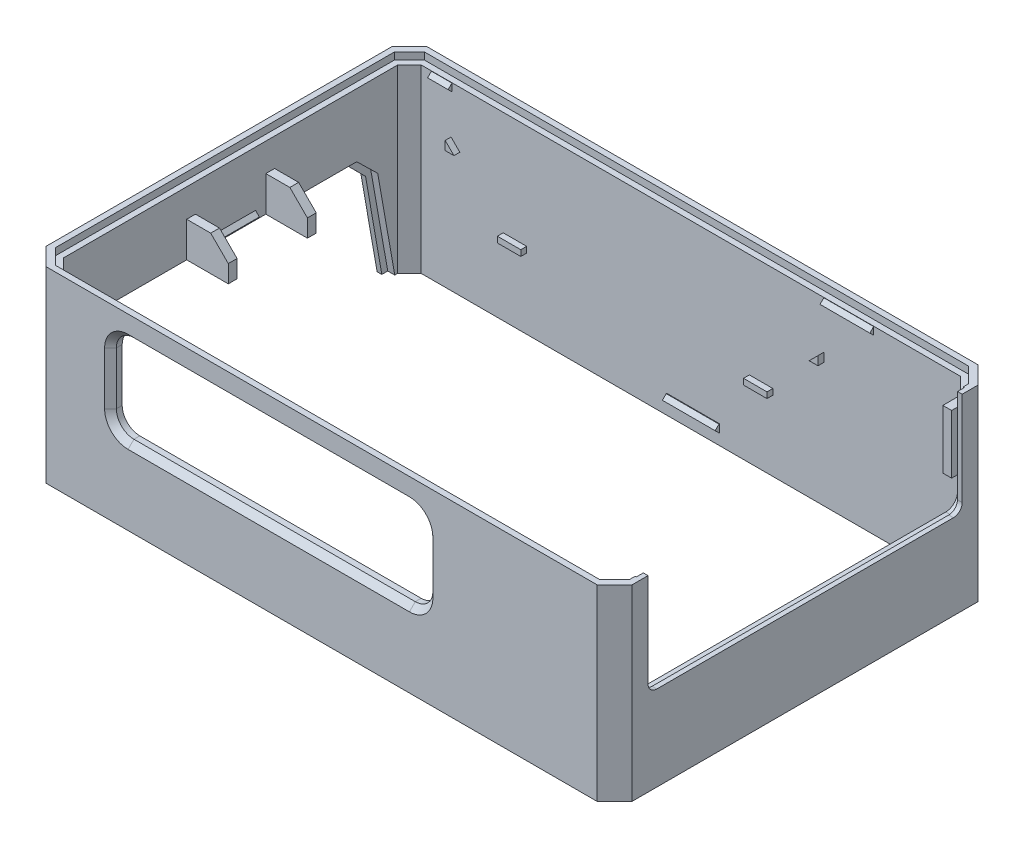
SolidWorks part; units mm, degrees
ref_plane "前视基准面" through (0, 0, 0) normal (0, 0, 1) x (1, 0, 0)
ref_plane "上视基准面" through (0, 0, 0) normal (0, 1, 0) x (1, 0, 0)
ref_plane "右视基准面" through (0, 0, 0) normal (1, 0, 0) x (0, 0, -1)
sketch "草图1" plane through (0, 0, 0) normal (0, 1, 0) x (1, 0, 0)
  line L1 (-50, 32.5) -> (50, 32.5)
  line L2 (-50, 32.5) -> (-50, -32.5)
  line L3 (-50, -32.5) -> (50, -32.5)
  line L4 (50, 32.5) -> (50, -32.5)
  line L5 (-50, 32.5) -> (50, -32.5) construction
  line L6 (-50, -32.5) -> (50, 32.5) construction
  point P0 (0, 0)
  dimension "D1" = 65
  dimension "D2" = 100
extrude "凸台-拉伸1" add sketch "草图1" along normal blind 32
sketch "草图2" plane through (0, 32, 0) normal (0, 1, 0) x (1, 0, 0)
  line L8 (48, -30.5) -> (48, 30.5)
  line L9 (48, 30.5) -> (-48, 30.5)
  line L10 (-48, 30.5) -> (-48, -30.5)
  line L11 (-48, -30.5) -> (48, -30.5)
  line L12 (48, -30.5) -> (48, 30.5)
  line L13 (48, 30.5) -> (-48, 30.5)
  line L14 (-48, 30.5) -> (-48, -30.5)
  line L15 (-48, -30.5) -> (48, -30.5)
  dimension "D1" = 2
extrude "切除-拉伸1" cut sketch "草图2" against normal through all
sketch "草图4" plane through (-50, 0, 0) normal (-1, 0, 0) x (0, 0, 1)
  line L0 (-32.5, 0) -> (32.5, 0) construction
  line L3 (-28, 0) -> (28, 0)
  line L7 (-25.0863, 16.5) -> (-21.5, 20)
  line L8 (21.5, 20) -> (25.09, 16.5)
  line L9 (32.5, 32) -> (32.5, 0) construction
  line L12 (-25.0863, 16.5) -> (-28, 0)
  line L13 (-21.5, 20) -> (21.5, 20)
  line L14 (25.09, 16.5) -> (28, 0)
  line L15 (-32.5, 0) -> (32.5, 0) construction
  line L16 (-32.5, 32) -> (-32.5, 0) construction
  dimension "D1" = 16.5
  dimension "D2" = 20
  dimension "D3" = 4.5
  dimension "D4" = 4.5
  dimension "D5" = 11
  dimension "D6" = 11
  dimension "D7" = 7.4137
  dimension "D8" = 7.41
extrude "切除-拉伸2" cut sketch "草图4" against normal blind 2
sketch "草图7" plane through (0, 0, 32.5) normal (0, 0, 1) x (1, 0, 0)
  line L0 (-50, 32) -> (-50, 0) construction
  line L5 (-50, 32) -> (50, 32) construction
  line L16 (-36, 28) -> (-36, 13)
  line L17 (18, 28) -> (-36, 28)
  line L18 (18, 13) -> (18, 28)
  line L19 (-36, 13) -> (18, 13)
  dimension "D1" = 54
  dimension "D2" = 15
  dimension "D3" = 14
  dimension "D4" = 4
extrude "切除-拉伸3" cut sketch "草图7" against normal blind 2.5
fillet "圆角7" radius 3 4 edges at (-36, 28, 31.5) (18, 28, 31.5) (18, 13, 31.5) (-36, 13, 31.5)
chamfer "倒角1" distance 1 angle 45 8 edges at (-9, 28, 32.5) (-35.1213, 27.1213, 32.5) (17.1213, 27.1213, 32.5) (-36, 20.5, 32.5) (18, 20.5, 32.5) (-35.1213, 13.8787, 32.5) (17.1213, 13.8787, 32.5) (-9, 13, 32.5)
ref_plane "基准面4" through (0, 19.25, 0) normal (0, -1, 0) x (-1, 0, 0)
sketch "草图17" plane through (-48, 0, 0) normal (1, 0, 0) x (0, 0, -1)
  line L1 (-6, 20) -> (-7.5, 20)
  line L2 (-6, 20) -> (-6, 26)
  line L3 (-6, 26) -> (-7.5, 26)
  line L4 (-7.5, 20) -> (-7.5, 26)
  line L5 (32.5, 32) -> (32.5, 0) construction
  line L6 (6, 20) -> (7.5, 20)
  line L7 (6, 20) -> (6, 26)
  line L8 (6, 26) -> (7.5, 26)
  line L9 (7.5, 20) -> (7.5, 26)
  line L10 (-21.5, 20) -> (21.5, 20) construction
  line L12 (-32.5, 32) -> (-32.5, 0) construction
  dimension "D1" = 1.5
  dimension "D2" = 1.5
  dimension "D3" = 25
  dimension "D4" = 25
  dimension "D5" = 6
extrude "凸台-拉伸6" add sketch "草图17" along normal blind 7.1
chamfer "倒角6" distance 3 angle 45 2 edges at (-40.9, 26, -6.75) (-40.9, 26, 6.75)
sketch "草图24" plane through (48, 0, 0) normal (-1, 0, 0) x (0, 0, 1)
  line L1 (-4.5, 3.3) -> (4.5, 3.3)
  line L2 (-4.5, 3.3) -> (-4.5, 1.8)
  line L3 (-4.5, 1.8) -> (4.5, 1.8)
  line L4 (4.5, 3.3) -> (4.5, 1.8)
  line L5 (-4.5, 3.3) -> (4.5, 1.8) construction
  line L6 (-4.5, 1.8) -> (4.5, 3.3) construction
  line L7 (30.5, 0) -> (-30.5, 0) construction
  line L8 (32.5, 0) -> (-32.5, 0) construction
  point P0 (0, 2.55)
  point P10 (0, 0)
  dimension "D1" = 1.5
  dimension "D2" = 1.8
  dimension "D3" = 9
extrude "凸台-拉伸10" add sketch "草图24" along normal blind 1
sketch "草图25" plane through (0, 0, 30.5) normal (0, 0, -1) x (-1, 0, 0)
  line L0 (48, 0) -> (-48, 0) construction
  line L1 (-4.9102, 3.2365) -> (4.0898, 3.2365)
  line L2 (-4.9102, 3.2365) -> (-4.9102, 1.9365)
  line L3 (-4.9102, 1.9365) -> (4.0898, 1.9365)
  line L4 (4.0898, 3.2365) -> (4.0898, 1.9365)
  line L5 (-4.9102, 3.2365) -> (4.0898, 1.9365) construction
  line L6 (-4.9102, 1.9365) -> (4.0898, 3.2365) construction
  line L8 (50, 32) -> (50, 0) construction
  point P0 (-0.4102, 2.5865)
  dimension "D1" = 9
  dimension "D2" = 1.3
  dimension "D3" = 2.5865
  dimension "D4" = 50.4102
extrude "凸台-拉伸11" add sketch "草图25" along normal blind 1
sketch "草图26" plane through (0, 0, -30.5) normal (0, 0, 1) x (1, 0, 0)
  line L4 (-4.0898, 3.2365) -> (-4.0898, 1.9365)
  line L5 (4.9102, 3.2365) -> (-4.0898, 3.2365)
  line L6 (4.9102, 1.9365) -> (4.9102, 3.2365)
  line L7 (-4.0898, 1.9365) -> (4.9102, 1.9365)
  line L8 (-4.0898, 3.2365) -> (-4.0898, 1.9365)
  line L9 (4.9102, 3.2365) -> (-4.0898, 3.2365)
  line L10 (4.9102, 1.9365) -> (4.9102, 3.2365)
  line L11 (-4.0898, 1.9365) -> (4.9102, 1.9365)
  dimension "D1" = 0
extrude "凸台-拉伸12" add sketch "草图26" along normal blind 1
chamfer "倒角7" distance 2 angle 45 4 edges at (-48, 16, -30.5) (-48, 16, 30.5) (48, 16, -30.5) (48, 16, 30.5)
chamfer "倒角8" distance 3 angle 45 4 edges at (-50, 16, 32.5) (-50, 16, -32.5) (50, 16, -32.5) (50, 16, 32.5)
sketch "草图28" plane through (-50, 0, 0) normal (-1, 0, 0) x (0, 0, 1)
  line L27 (-29.3, 22.3393) -> (-29.3, 0)
  line L28 (-29.3, 0) -> (-26.9872, 0)
  line L29 (-26.9872, 0) -> (-24.2154, 15.8784)
  line L30 (-24.2154, 15.8784) -> (-21.1176, 18.9896)
  line L31 (-21.1176, 18.9896) -> (21.1176, 18.9896)
  line L32 (21.1176, 18.9896) -> (24.2152, 15.8784)
  line L33 (24.2152, 15.8784) -> (27.008, 0)
  line L34 (27.008, 0) -> (29.3, 0)
  line L35 (29.3, 0) -> (29.3, 22.3393)
  line L36 (29.3, 22.3393) -> (-29.3, 22.3393)
  line L37 (28.5, 0) -> (-28.5, 0) construction
  line L38 (-29.5, 0) -> (-28, 0) construction
  line L39 (28, 0) -> (29.5, 0) construction
extrude "凸台-拉伸13" add sketch "草图28" against normal blind 0.8
sketch "草图35" plane through (48, 0, 0) normal (-1, 0, 0) x (0, 0, 1)
  line L0 (-28, 32) -> (28, 32)
  line L1 (-28, 32) -> (-28, 14)
  line L2 (-28, 14) -> (28, 14)
  line L3 (28, 32) -> (28, 14)
  line L4 (32.5, 0) -> (32.5, 32) construction
  line L5 (-32.5, 32) -> (-32.5, 0) construction
  line L6 (28.5, 32) -> (-28.5, 32) construction
  dimension "D1" = 18
  dimension "D3" = 4.5
  dimension "D4" = 4.5
extrude "切除-拉伸6" cut sketch "草图35" against normal blind 1.2
fillet "圆角17" radius 2 2 edges at (48.6, 14, -28) (48.6, 14, 28)
sketch "草图39" plane through (49.2, 0, 0) normal (-1, 0, 0) x (0, 0, 1)
  line L0 (32.5, 0) -> (32.5, 32) construction
  line L1 (-32.5, 32) -> (-32.5, 0) construction
  line L2 (28, 32) -> (-28, 32) construction
  line L3 (29.5, 32) -> (-29.5, 32) construction
  line L4 (29.5, 0) -> (-29.5, 0) construction
  line L12 (-26.8, 32) -> (-26.8, 16)
  line L13 (-25.3, 14.5) -> (25.3, 14.5)
  line L14 (26.8, 16) -> (26.8, 32)
  line L15 (26.8, 32) -> (-26.8, 32)
  arc A6 (-26.8, 16) -> (-25.3, 14.5) centre (-25.3, 16) ccw
  arc A7 (25.3, 14.5) -> (26.8, 16) centre (25.3, 16) ccw
  dimension "D1" = 7.2
  dimension "D2" = 7.2
  dimension "D3" = 16
  dimension "D4" = 14.5
extrude "切除-拉伸7" cut sketch "草图39" against normal blind 1.2
ref_plane "基准面5" through (-50, 32, 29.5) normal (0.7071, 0, 0.7071) x (0.7071, 0, -0.7071)
sketch "草图44" plane through (0, 0, -28) normal (0, 0, 1) x (1, 0, 0)
  line L0 (48, 32) -> (48, 16) construction
  line L1 (48, 28.5) -> (46.5, 28.5)
  line L2 (48, 28.5) -> (48, 18.5)
  line L3 (48, 18.5) -> (46.5, 18.5)
  line L4 (46.5, 28.5) -> (46.5, 18.5)
  line L5 (50, 14.5) -> (49.2, 14.5) construction
  dimension "D1" = 1.5
  dimension "D2" = 10
  dimension "D3" = 4
extrude "凸台-拉伸15" add sketch "草图44" along normal blind 1 and the other way up to surface (2.5 mm away) other way up to face at (0, 16, -30.5)
sketch "草图45" plane through (0, 0, 28) normal (0, 0, -1) x (-1, 0, 0)
  line L4 (-48, 28.5) -> (-48, 18.5)
  line L5 (-46.5, 28.5) -> (-48, 28.5)
  line L6 (-46.5, 18.5) -> (-46.5, 28.5)
  line L7 (-48, 18.5) -> (-46.5, 18.5)
  line L8 (-48, 28.5) -> (-48, 18.5)
  line L9 (-46.5, 28.5) -> (-48, 28.5)
  line L10 (-46.5, 18.5) -> (-46.5, 28.5)
  line L11 (-48, 18.5) -> (-46.5, 18.5)
  dimension "D1" = 0
extrude "凸台-拉伸16" add sketch "草图45" along normal blind 1 and the other way up to surface (2.5 mm away) other way up to face at (0, 16, 30.5)
ref_plane "基准面6" through (48, 0, -28.5) normal (0, 0, -1) x (-1, 0, 0)
sketch "草图48" plane through (0, 32, 0) normal (0, 1, 0) x (1, 0, 0)
  line L0 (48, 28.5) -> (46, 30.5)
  line L1 (46, 30.5) -> (-46, 30.5)
  line L2 (48, 28.5) -> (48, -28.5)
  line L3 (46, -30.5) -> (-46, -30.5)
  line L4 (-48, 28.5) -> (-48, -28.5)
  line L5 (48, -28.5) -> (46, -30.5)
  line L6 (-46, -30.5) -> (-48, -28.5)
  line L7 (-46, 30.5) -> (-48, 28.5)
  line L8 (49, 28.9142) -> (49, -28.9142)
  line L9 (49, -28.9142) -> (46.4142, -31.5)
  line L10 (46.4142, -31.5) -> (-46.4142, -31.5)
  line L11 (-46.4142, -31.5) -> (-49, -28.9142)
  line L12 (-49, 28.9142) -> (-49, -28.9142)
  line L13 (-46.4142, 31.5) -> (-49, 28.9142)
  line L14 (46.4142, 31.5) -> (-46.4142, 31.5)
  line L15 (49, 28.9142) -> (46.4142, 31.5)
  point P0 (48, 30.5)
  point P1 (-48, -30.5)
  point P2 (48, -30.5)
  point P3 (-48, 30.5)
  dimension "D2" = 1
extrude "切除-拉伸8" cut sketch "草图48" against normal blind 1.2
sketch "草图49" plane through (0, 0, -30.5) normal (0, 0, 1) x (1, 0, 0)
  line L0 (50, 32) -> (50, 16) construction
  line L1 (22.6985, 30.75) -> (31.1985, 30.75)
  line L2 (22.6985, 30.75) -> (22.6985, 29.45)
  line L3 (22.6985, 29.45) -> (31.1985, 29.45)
  line L4 (31.1985, 30.75) -> (31.1985, 29.45)
  line L5 (22.6985, 30.75) -> (31.1985, 29.45) construction
  line L6 (22.6985, 29.45) -> (31.1985, 30.75) construction
  line L7 (-47, 32) -> (47, 32) construction
  line L8 (46.4142, 32) -> (-46.4142, 32) construction
  line L9 (-44.25, 30.75) -> (-40.75, 30.75)
  line L10 (-44.25, 30.75) -> (-44.25, 29.45)
  line L11 (-44.25, 29.45) -> (-40.75, 29.45)
  line L12 (-40.75, 30.75) -> (-40.75, 29.45)
  line L13 (-44.25, 30.75) -> (-40.75, 29.45) construction
  line L14 (-44.25, 29.45) -> (-40.75, 30.75) construction
  line L15 (-50, 0) -> (-50, 32) construction
  point P0 (26.9485, 30.1)
  point P7 (-42.5, 30.1)
  dimension "D1" = 1.3
  dimension "D2" = 8.5
  dimension "D3" = 18.8015
  dimension "D4" = 1.9
  dimension "D5" = 1.3
  dimension "D6" = 1.9
  dimension "D7" = 5.75
  dimension "D8" = 3.5
extrude "凸台-拉伸17" add sketch "草图49" along normal blind 0.8
sketch "草图50" plane through (0, 0, 30.5) normal (0, 0, -1) x (-1, 0, 0)
  line L0 (40.75, 29.45) -> (40.75, 30.75) construction
  line L1 (40.75, 30.75) -> (44.25, 30.75) construction
  line L2 (44.25, 30.75) -> (44.25, 29.45) construction
  line L3 (44.25, 29.45) -> (40.75, 29.45) construction
  line L4 (-31.1985, 29.45) -> (-31.1985, 30.75) construction
  line L5 (-31.1985, 30.75) -> (-22.6985, 30.75) construction
  line L6 (-22.6985, 30.75) -> (-22.6985, 29.45) construction
  line L7 (-22.6985, 29.45) -> (-31.1985, 29.45) construction
  line L12 (40.75, 29.45) -> (40.75, 30.75)
  line L13 (40.75, 30.75) -> (44.25, 30.75)
  line L14 (44.25, 30.75) -> (44.25, 29.45)
  line L15 (44.25, 29.45) -> (40.75, 29.45)
  line L16 (-31.1985, 29.45) -> (-31.1985, 30.75)
  line L17 (-31.1985, 30.75) -> (-22.6985, 30.75)
  line L18 (-22.6985, 30.75) -> (-22.6985, 29.45)
  line L19 (-22.6985, 29.45) -> (-31.1985, 29.45)
extrude "凸台-拉伸18" add sketch "草图50" along normal blind 0.8
sketch "草图55" plane through (0, 0, -30.5) normal (0, 0, 1) x (1, 0, 0)
  line L0 (-50, 0) -> (-50, 32) construction
  line L1 (-23, 20) -> (5.5, 20)
  line L2 (-23, 20) -> (-23, 18.6)
  line L3 (-23, 18.6) -> (5.5, 18.6)
  line L4 (5.5, 20) -> (5.5, 18.6)
  line L5 (-47, 32) -> (47, 32) construction
  dimension "D1" = 1.4
  dimension "D2" = 27
  dimension "D3" = 12
  dimension "D4" = 28.5
sketch "草图56" plane through (0, 0, -30.5) normal (0, 0, 1) x (1, 0, 0)
  line L0 (-50, 0) -> (-50, 32) construction
  line L1 (-23, 24) -> (-21.5, 24)
  line L2 (-23, 24) -> (-23, 16)
  line L3 (-23, 16) -> (-21.5, 16)
  line L4 (-21.5, 24) -> (-21.5, 16)
  line L5 (4, 24) -> (5.5, 24)
  line L6 (4, 24) -> (4, 16)
  line L7 (4, 16) -> (5.5, 16)
  line L8 (5.5, 24) -> (5.5, 16)
  line L9 (-47, 32) -> (47, 32) construction
  dimension "D1" = 1.5
  dimension "D2" = 8
  dimension "D3" = 27
  dimension "D4" = 54
  dimension "D5" = 8
chamfer "倒角11" distance 0.8 angle 45 8 edges at (-42.5, 30.75, 29.7) (-42.5, 29.45, 29.7) (26.9485, 29.45, -29.7) (26.9485, 30.75, -29.7) (26.9485, 30.75, 29.7) (26.9485, 29.45, 29.7) (-42.5, 29.45, -29.7) (-42.5, 30.75, -29.7)
chamfer "倒角12" distance 0.9 angle 45 4 edges at (0.4102, 1.9365, 29.5) (0.4102, 3.2365, 29.5) (0.4102, 1.9365, -29.5) (0.4102, 3.2365, -29.5)
chamfer "倒角13" distance 0.9 angle 45 2 edges at (47, 1.8, 0) (47, 3.3, 0)
sketch "草图57" plane through (0, 0, 30.5) normal (0, 0, -1) x (-1, 0, 0)
  line L1 (-21.2, 21.2) -> (-22.7, 21.2)
  line L2 (-21.2, 21.2) -> (-21.2, 22.7)
  line L3 (-21.2, 22.7) -> (-22.7, 22.7)
  line L4 (-22.7, 21.2) -> (-22.7, 22.7)
  line L5 (39.4, 21.2) -> (40.9, 21.2)
  line L6 (39.4, 21.2) -> (39.4, 22.7)
  line L7 (39.4, 22.7) -> (40.9, 22.7)
  line L8 (40.9, 21.2) -> (40.9, 22.7)
  line L9 (47, 32) -> (-47, 32) construction
  line L10 (-50, 32) -> (-50, 0) construction
  line L11 (50, 0) -> (50, 32) construction
  line L12 (46, 0) -> (-46, 0) construction
  line L17 (-14, 9) -> (-10, 9)
  line L18 (-14, 9) -> (-14, 8)
  line L19 (-14, 8) -> (-10, 8)
  line L20 (-10, 9) -> (-10, 8)
  line L21 (28, 9) -> (32, 9)
  line L22 (28, 9) -> (28, 8)
  line L23 (28, 8) -> (32, 8)
  line L24 (32, 9) -> (32, 8)
  dimension "D1" = 1.5
  dimension "D2" = 10.8
  dimension "D3" = 28.8
  dimension "D4" = 10.6
  dimension "D5" = 4
  dimension "D6" = 4
  dimension "D7" = 1
  dimension "D8" = 1
  dimension "D9" = 9
  dimension "D10" = 18
  dimension "D11" = 60
extrude "凸台-拉伸24" add sketch "草图57" along normal blind 1.5
chamfer "倒角14" distance 1.5 angle 45 2 edges at (21.2, 22.7, 29.75) (-39.4, 22.7, 29.75)
sketch "草图58" plane through (0, 0, -30.5) normal (0, 0, 1) x (1, 0, 0)
  line L20 (22.7, 21.2) -> (21.2, 21.2) construction
  line L21 (21.2, 21.2) -> (22.7, 22.7) construction
  line L22 (22.7, 22.7) -> (22.7, 21.2) construction
  line L23 (-40.9, 21.2) -> (-40.9, 22.7) construction
  line L24 (-40.9, 22.7) -> (-39.4, 21.2) construction
  line L25 (-39.4, 21.2) -> (-40.9, 21.2) construction
  line L26 (22.7, 21.2) -> (21.2, 21.2)
  line L27 (21.2, 21.2) -> (22.7, 22.7)
  line L28 (14, 13) -> (14, 12)
  line L29 (14, 12) -> (10, 12)
  line L30 (10, 12) -> (10, 13)
  line L31 (10, 13) -> (14, 13)
  line L32 (-28, 13) -> (-28, 12)
  line L33 (-28, 12) -> (-32, 12)
  line L34 (-32, 12) -> (-32, 13)
  line L35 (-32, 13) -> (-28, 13)
  line L36 (-50, 32) -> (-50, 0) construction
  line L37 (46, 0) -> (-46, 0) construction
  line L38 (22.7, 22.7) -> (22.7, 21.2)
  line L39 (-40.9, 21.2) -> (-40.9, 22.7)
  line L40 (-40.9, 22.7) -> (-39.4, 21.2)
  line L41 (-39.4, 21.2) -> (-40.9, 21.2)
  dimension "D1" = 18
  dimension "D2" = 60
  dimension "D3" = 1
  dimension "D4" = 4
  dimension "D5" = 4
  dimension "D6" = 12
extrude "凸台-拉伸25" add sketch "草图58" along normal blind 1
sketch "草图59" plane through (-48, 0, 0) normal (1, 0, 0) x (0, 0, -1)
  line L0 (29.5, 32) -> (-29.5, 32) construction
  line L1 (-4.25, 21.4396) -> (4.25, 21.4396)
  line L2 (-4.25, 21.4396) -> (-4.25, 20.1396)
  line L3 (-4.25, 20.1396) -> (4.25, 20.1396)
  line L4 (4.25, 21.4396) -> (4.25, 20.1396)
  line L5 (-4.25, 21.4396) -> (4.25, 20.1396) construction
  line L6 (-4.25, 20.1396) -> (4.25, 21.4396) construction
  line L7 (21.1176, 18.9896) -> (-21.1176, 18.9896) construction
  point P0 (0, 20.7896)
  point P7 (0, 32)
  dimension "D1" = 8.5
  dimension "D2" = 1.3
  dimension "D3" = 1.8
extrude "凸台-拉伸26" add sketch "草图59" along normal blind 0.8
chamfer "倒角15" distance 0.8 angle 45 2 edges at (-47.2, 20.1396, 0) (-47.2, 21.4396, 0)
